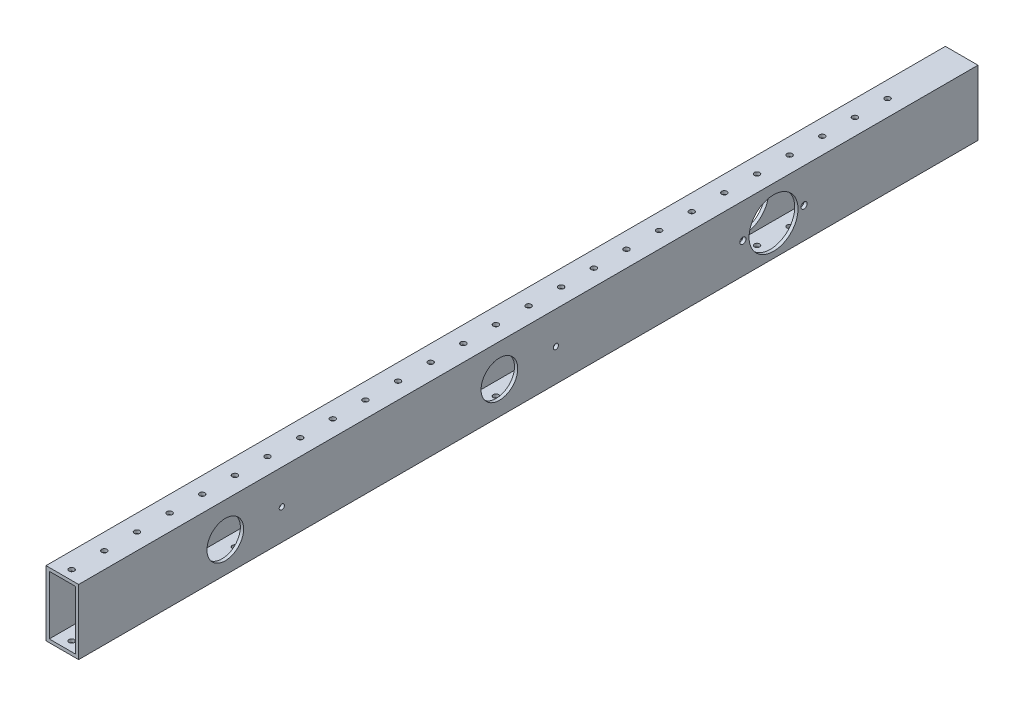
SolidWorks part; units mm, degrees
material "2014-T6"
ref_plane "Alzado" through (0, 0, 0) normal (0, 0, 1) x (1, 0, 0)
ref_plane "Planta" through (0, 0, 0) normal (0, 1, 0) x (1, 0, 0)
ref_plane "Vista lateral" through (0, 0, 0) normal (1, 0, 0) x (0, 0, -1)
sketch "Croquis1" plane through (0, 0, 0) normal (0, 0, 1) x (1, 0, 0)
  line L1 (-12.7, 25.35) -> (12.7, 25.35)
  line L2 (-12.7, 25.35) -> (-12.7, -25.35)
  line L3 (-12.7, -25.35) -> (12.7, -25.35)
  line L4 (12.7, 25.35) -> (12.7, -25.35)
  line L5 (-12.7, 25.35) -> (12.7, -25.35) construction
  line L6 (-12.7, -25.35) -> (12.7, 25.35) construction
  line L7 (-10.16, 22.81) -> (10.16, 22.81)
  line L8 (-10.16, 22.81) -> (-10.16, -22.81)
  line L9 (-10.16, -22.81) -> (10.16, -22.81)
  line L10 (10.16, 22.81) -> (10.16, -22.81)
  line L11 (-10.16, 22.81) -> (10.16, -22.81) construction
  line L12 (-10.16, -22.81) -> (10.16, 22.81) construction
  point P0 (0, 0)
  point P6 (0, 0)
  dimension "D1" = 25.4
  dimension "D2" = 50.7
  dimension "D3" = 2.54
  dimension "D4" = 2.54
extrude "Saliente-Extruir1" add sketch "Croquis1" along normal blind 655
sketch "Croquis2" plane through (0, 25.35, 0) normal (0, 1, 0) x (1, 0, 0)
  line L0 (-12.7, 0) -> (12.7, 0)
  line L1 (12.7, 0) -> (0, 0)
  line L2 (0, 0) -> (0, -655)
  line L3 (12.7, -655) -> (-12.7, -655) construction
  circle A0 centre (0, -12.7) radius 2.07
  circle A1 centre (0, -38.1) radius 2.07
  circle A2 centre (0, -63.5) radius 2.07
  circle A3 centre (0, -88.9) radius 2.07
  circle A4 centre (0, -114.3) radius 2.07
  circle A5 centre (0, -139.7) radius 2.07
  circle A6 centre (0, -165.1) radius 2.07
  circle A7 centre (0, -190.5) radius 2.07
  circle A8 centre (0, -215.9) radius 2.07
  circle A9 centre (0, -241.3) radius 2.07
  circle A10 centre (0, -266.7) radius 2.07
  circle A11 centre (0, -292.1) radius 2.07
  circle A12 centre (0, -317.5) radius 2.07
  circle A13 centre (0, -342.9) radius 2.07
  circle A14 centre (0, -368.3) radius 2.07
  circle A15 centre (0, -393.7) radius 2.07
  circle A16 centre (0, -419.1) radius 2.07
  circle A17 centre (0, -444.5) radius 2.07
  circle A18 centre (0, -469.9) radius 2.07
  circle A19 centre (0, -495.3) radius 2.07
  circle A20 centre (0, -520.7) radius 2.07
  circle A21 centre (0, -546.1) radius 2.07
  circle A22 centre (0, -571.5) radius 2.07
  circle A23 centre (0, -596.9) radius 2.07
  circle A24 centre (0, -622.3) radius 2.07
  circle A25 centre (0, -647.7) radius 2.07
  dimension "D1" = 4.14
  dimension "D2" = 12.7
  dimension "D3" = 26
extrude "Cortar-Extruir1" cut sketch "Croquis2" against normal through all contours A0 | A1 | A2 | A3 | A4 | A5 | A6 | A7 | A8 | A9 | A10 | A11 | A12 | A13 | A14 | A15 | A16 | A17 | A18 | A19 | A20 | A21 | A22 | A23 | A24 | A25
sketch "Croquis3" plane through (-12.7, 0, 0) normal (-1, 0, 0) x (0, 0, 1)
  line L0 (0, 0) -> (327.5, 0)
  circle A0 centre (327.5, 0) radius 14.275
  dimension "D2" = 28.55
  dimension "D1" = 327.5
extrude "Cortar-Extruir2" cut sketch "Croquis3" against normal blind 700 contours A0
sketch "Croquis4" plane through (-12.7, 0, 0) normal (-1, 0, 0) x (0, 0, 1)
  circle A0 centre (303.9553, 0) radius 2.41
  dimension "D1" = 4.82
sketch "Croquis5" plane through (-12.7, 0, 0) normal (-1, 0, 0) x (0, 0, 1)
  line L0 (327.5, -25.35) -> (327.5926, 25.3498)
  line L2 (655, -25.35) -> (0, -25.35) construction
  line L3 (327.5926, 25.3498) -> (351.3125, 25.3498)
  line L4 (351.3125, 25.3498) -> (351.3125, -25.35)
  line L5 (351.3125, -25.35) -> (302.5949, -25.35)
  line L6 (302.5949, -25.35) -> (302.5949, 25.3498)
  line L7 (302.5949, 25.3498) -> (327.5926, 25.3498)
  line L8 (327.5, -25.35) -> (327.5463, -0.0001)
  line L9 (327.5463, -0.0001) -> (367.7335, -0.0735)
  line L10 (367.7335, -0.0735) -> (294.1923, 0.0608)
  circle A0 centre (351.3125, 0) radius 3.1556
sketch "Croquis6" plane through (-12.7, 0, 0) normal (-1, 0, 0) x (0, 0, 1)
  line L0 (82.895, 0) -> (478.5071, 0)
  circle A1 centre (303.6875, 0) radius 2.41
  circle A2 centre (351.3125, 0) radius 2.41
  circle A3 centre (354.42, 1.3931) radius 0.0224
  dimension "D1" = 4.82
sketch "Croquis7" plane through (-12.7, 0, 0) normal (-1, 0, 0) x (0, 0, 1)
  circle A0 centre (114.1451, -1.474) radius 14.2748
sketch "Croquis8" plane through (-12.7, 0, 0) normal (-1, 0, 0) x (0, 0, 1)
  circle A0 centre (114.1451, -1.474) radius 19.05
  circle A1 centre (540.8549, -1.474) radius 14.2748
  dimension "D1" = 28.5496
  dimension "D2" = 38.1
extrude "Cortar-Extruir5" cut sketch "Croquis8" against normal blind 700
sketch "Croquis9" plane through (-12.7, 0, 0) normal (-1, 0, 0) x (0, 0, 1)
  line L1 (655, 25.35) -> (0, 25.35) construction
  line L4 (655, -25.35) -> (0, -25.35) construction
  line L6 (158.1451, -3.494) -> (158.1451, -3.4693)
  line L7 (158.1451, 0.5693) -> (158.1451, 0.546)
  line L8 (158.1451, -1.45) -> (158.1451, -1.474)
  line L9 (156.1251, -1.474) -> (156.126, -1.474)
  line L10 (158.1451, 0.5693) -> (158.1451, 0.546)
  line L11 (540.8409, -1.4697) -> (540.8334, -1.494)
  line L12 (540.8334, -1.494) -> (480.5107, -1.494)
  line L13 (480.5107, -1.494) -> (480.5107, 25.35)
  line L14 (480.5107, 25.35) -> (489.2424, 25.35)
  line L15 (489.2424, 25.35) -> (489.2424, -25.35)
  line L16 (489.2424, -25.35) -> (496.8549, -1.45)
  line L17 (496.8549, -1.45) -> (489.2424, -25.35)
  line L18 (496.8549, -1.45) -> (496.8549, 25.35)
  line L19 (496.8549, 25.35) -> (496.8549, -25.35)
  line L20 (158.1451, 0.546) -> (158.1451, 0.5693)
  line L21 (160.1643, -1.474) -> (160.1651, -1.474)
  line L22 (158.1451, -1.474) -> (158.1451, -1.45)
  line L23 (158.1451, -3.4693) -> (158.1451, -3.494)
  arc A0 (156.1264, -1.4031) -> (156.126, -1.474) centre (158.1451, -1.45) ccw
  arc A1 (156.1264, -1.4031) -> (156.1251, -1.474) centre (158.1451, -1.474) ccw
  circle A2 centre (496.8409, -1.494) radius 2.02
  arc A3 (160.1643, -1.474) -> (160.1639, -1.4031) centre (158.1451, -1.45) ccw
  arc A4 (160.1651, -1.474) -> (160.1639, -1.4031) centre (158.1451, -1.474) ccw
  dimension "D1" = 4.04
  dimension "D2" = 4.04
  dimension "D3" = 44
sketch "Croquis10" plane through (12.7, 0, 0) normal (1, 0, 0) x (0, 0, -1)
  line L0 (-655, 25.35) -> (0, 25.35) construction
  circle A0 centre (-496.8549, -1.45) radius 2.02
  circle A1 centre (-540.8549, -1.474) radius 14.2748 construction
  dimension "D1" = 4.04
  dimension "D2" = 44
  dimension "D3" = 26.8
extrude "Cortar-Extruir7" cut sketch "Croquis10" against normal through all
sketch "Croquis12" plane through (12.7, 0, 0) normal (1, 0, 0) x (0, 0, -1)
  circle A0 centre (-283.5, 0) radius 2.02
  circle A1 centre (-327.5, 0) radius 14.275 construction
  dimension "D1" = 44
  dimension "D2" = 0
  dimension "D3" = 4.04
extrude "Cortar-Extruir8" cut sketch "Croquis12" against normal through all
sketch "Croquis14" plane through (-12.7, 0, 0) normal (-1, 0, 0) x (0, 0, 1)
  line L0 (0, 25.35) -> (0, -25.35) construction
  circle A1 centre (138, 0) radius 2.41
  dimension "D2" = 4.82
  dimension "D3" = 138
sketch "Croquis15" plane through (-12.7, 0, 0) normal (-1, 0, 0) x (0, 0, 1)
  circle A0 centre (137.9576, -1.474) radius 2.4095
  circle A1 centre (90.3326, -1.474) radius 2.413
extrude "Cortar-Extruir10" cut sketch "Croquis15" against normal through all
sketch "Croquis16" plane through (0, 0, 0) normal (0, 0, -1) x (-1, 0, 0)
  line L1 (-10.16, -22.81) -> (10.16, -22.81)
  line L2 (-10.16, -22.81) -> (-10.16, 22.81)
  line L3 (-10.16, 22.81) -> (10.16, 22.81)
  line L4 (10.16, -22.81) -> (10.16, 22.81)
  line L5 (-10.16, -22.81) -> (10.16, 22.81) construction
  line L6 (-10.16, 22.81) -> (10.16, -22.81) construction
  line L7 (-12.7, -25.35) -> (12.7, -25.35)
  line L8 (-12.7, -25.35) -> (-12.7, 25.35)
  line L9 (-12.7, 25.35) -> (12.7, 25.35)
  line L10 (12.7, -25.35) -> (12.7, 25.35)
  line L11 (-12.7, -25.35) -> (12.7, 25.35) construction
  line L12 (-12.7, 25.35) -> (12.7, -25.35) construction
  point P0 (0, 0)
  point P7 (0, 0)
extrude "Saliente-Extruir2" add sketch "Croquis16" along normal blind 45
